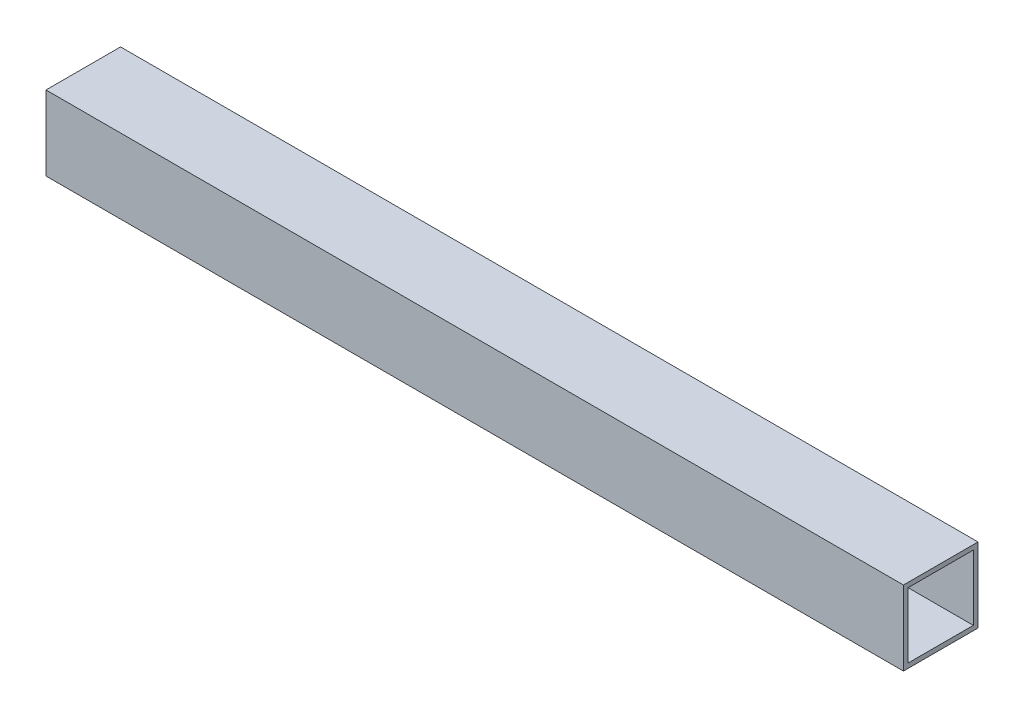
SolidWorks part; units mm, degrees
material "6061-T6 (SS)"
ref_plane "Front" through (0, 0, 0) normal (0, 0, 1) x (1, 0, 0)
ref_plane "Top" through (0, 0, 0) normal (0, 1, 0) x (1, 0, 0)
ref_plane "Right" through (0, 0, 0) normal (1, 0, 0) x (0, 0, -1)
sketch "Sketch1" plane through (0, 0, 0) normal (1, 0, 0) x (0, 0, -1)
  line L1 (12.7, -12.7) -> (-12.7, -12.7)
  line L2 (12.7, -12.7) -> (12.7, 12.7)
  line L3 (12.7, 12.7) -> (-12.7, 12.7)
  line L4 (-12.7, -12.7) -> (-12.7, 12.7)
  line L5 (12.7, -12.7) -> (-12.7, 12.7) construction
  line L6 (12.7, 12.7) -> (-12.7, -12.7) construction
  point P0 (0, 0)
  dimension "D1" = 25.4
extrude "Extrude-Thin1" add sketch "Sketch1" along normal up to surface (292.1 mm away) thin thin type one direction reverse wall 1.5875
